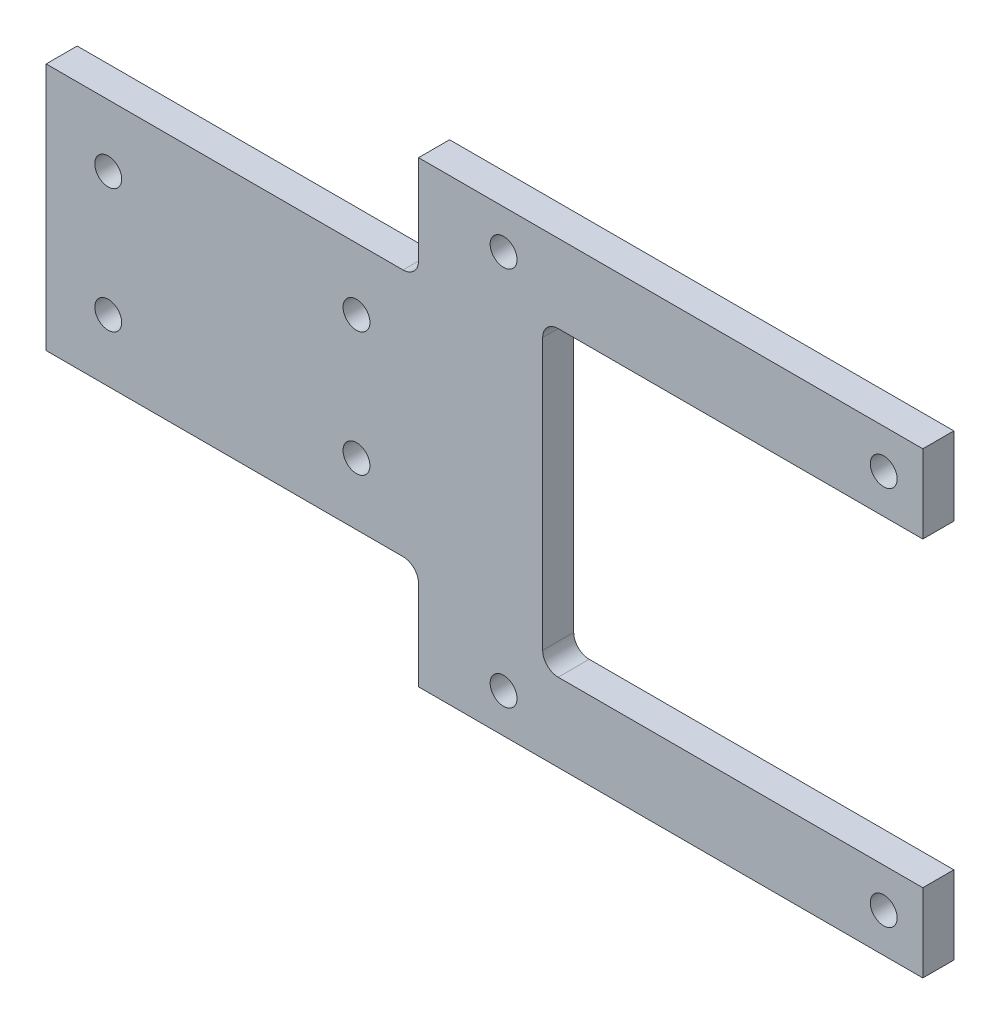
SolidWorks part; units mm, degrees
ref_plane "Front" through (0, 0, 0) normal (0, 0, 1) x (1, 0, 0)
ref_plane "Top" through (0, 0, 0) normal (0, 1, 0) x (1, 0, 0)
ref_plane "Right" through (0, 0, 0) normal (1, 0, 0) x (0, 0, -1)
sketch "Sketch1" plane through (0, 0, 0) normal (0, 0, 1) x (1, 0, 0)
  line L0 (38.1, 25.4) -> (38.1, 46.8909)
  line L1 (38.1, 25.4) -> (-38.1, 25.4)
  line L3 (38.1, -25.4) -> (-38.1, -25.4)
  line L4 (-38.1, 25.4) -> (-38.1, -25.4)
  line L5 (38.1, 25.4) -> (-38.1, -25.4) construction
  line L6 (38.1, -25.4) -> (-38.1, 25.4) construction
  line L7 (38.1, 46.8909) -> (141.2817, 46.8909)
  line L8 (141.2817, 46.8909) -> (141.2817, 30.8909)
  line L9 (141.2817, 30.8909) -> (63.5, 30.8909)
  line L10 (63.5, 30.8909) -> (63.5, -30.8909)
  line L11 (63.5, -30.8909) -> (141.2817, -30.8909)
  line L12 (141.2817, -30.8909) -> (141.2817, -46.8909)
  line L13 (141.2817, -46.8909) -> (38.1, -46.8909)
  line L14 (38.1, -46.8909) -> (38.1, -25.4)
  line L15 (38.1, 25.4) -> (63.5, 0) construction
  line L16 (63.5, 0) -> (38.1, -25.4) construction
  line L17 (0, 0) -> (94.3909, 0) construction
  line L18 (133.2817, -38.8909) -> (55.5, 38.8909) construction
  line L19 (133.2817, 38.8909) -> (55.5, -38.8909) construction
  line L20 (63.5, 30.8909) -> (94.3909, 0) construction
  line L21 (94.3909, 0) -> (63.5, -30.8909) construction
  line L22 (133.2817, 38.8909) -> (133.2817, 46.8909) construction
  line L23 (133.2817, 38.8909) -> (141.2817, 38.8909) construction
  line L24 (133.2817, 38.8909) -> (133.2817, 30.8909) construction
  line L25 (55.5, 38.8909) -> (38.1, 38.8909) construction
  circle A0 centre (94.3909, 0) radius 55 construction
  point P0 (0, 0)
  point P12 (50.1275, 29.3659)
  point P17 (133.2817, 38.8909)
  point P18 (133.2817, -38.8909)
  point P19 (55.5, 38.8909)
  point P20 (55.5, -38.8909)
  point P29 (-32.9423, 25.4)
  point P30 (44.45, 0)
  dimension "D2" = 110
  dimension "D1" = 50.8
  dimension "D3" = 45
  dimension "D4" = 45
  dimension "D5" = 90
  dimension "D6" = 8
  dimension "D7" = 76.2
  dimension "D8" = 25.4
extrude "Boss-Extrude1" add sketch "Sketch1" along normal blind 6.35
hole_wizard "M5 Clearance Hole1" positions "Sketch3" profile "Sketch4" hole size "M5" standard "ANSI Metric"
sketch "Sketch3" plane through (0, 0, 6.35) normal (0, 0, 1) x (1, 0, 0)
  line L0 (0, 0) -> (94.3909, 0) construction
  line L2 (133.2817, -38.8909) -> (55.5, 38.8909) construction
  line L4 (133.2817, 38.8909) -> (55.5, -38.8909) construction
  line L6 (63.5, 30.8909) -> (94.3909, 0) construction
  line L7 (94.3909, 0) -> (63.5, -30.8909) construction
  circle A0 centre (94.3909, 0) radius 55 construction
  point P0 (133.2817, 38.8909)
  point P2 (133.2817, -38.8909)
  point P4 (55.5, 38.8909)
  point P6 (55.5, -38.8909)
  dimension "D1" = 110
  dimension "D2" = 45
  dimension "D3" = 45
  dimension "D4" = 90
sketch "Sketch4" plane through (133.2817, 38.8909, 6.35) normal (1, 0, 0) x (0, -1, 0)
  line L0 (0, 0) -> (0, 20.4024)
  line L1 (0, 20.4024) -> (2.75, 18.75)
  line L2 (2.75, 18.75) -> (2.75, 0)
  line L5 (2.75, 0) -> (0, 0)
  line L10 (0, 20.4024) -> (-2.75, 18.75) construction
  line L11 (0, -6.35) -> (0, 107.95) construction
  dimension "Hole Dia." = 5.5
  dimension "Hole Depth" = 18.75
  dimension "Drill Angle" = 118
fillet "Fillet1" radius 3.175 4 edges at (63.5, 30.8909, 3.175) (63.5, -30.8909, 3.175) (38.1, -25.4, 3.175) (38.1, 25.4, 3.175)
hole_wizard "M5 Clearance Hole2" positions "Sketch5" profile "Sketch6" hole size "M5" standard "ANSI Metric"
sketch "Sketch5" plane through (0, 0, 6.35) normal (0, 0, 1) x (1, 0, 0)
  line L0 (-25.4, 12.7) -> (25.4, 12.7) construction
  line L1 (25.4, 12.7) -> (25.4, -12.7) construction
  line L2 (25.4, -12.7) -> (-25.4, -12.7) construction
  line L3 (-25.4, -12.7) -> (-25.4, 12.7) construction
  line L5 (34.925, 25.4) -> (-38.1, 25.4) construction
  line L6 (-38.1, -25.4) -> (34.925, -25.4) construction
  line L7 (-38.1, 25.4) -> (-38.1, -25.4) construction
  line L8 (63.5, -27.7159) -> (63.5, 27.7159) construction
  point P0 (-25.4, 12.7)
  point P2 (25.4, 12.7)
  point P4 (25.4, -12.7)
  point P6 (-25.4, -12.7)
  dimension "D1" = 12.7
  dimension "D2" = 12.7
  dimension "D3" = 12.7
  dimension "D4" = 38.1
sketch "Sketch6" plane through (-25.4, 12.7, 6.35) normal (1, 0, 0) x (0, -1, 0)
  line L0 (0, 0) -> (0, 20.4024)
  line L1 (0, 20.4024) -> (2.75, 18.75)
  line L2 (2.75, 18.75) -> (2.75, 0)
  line L5 (2.75, 0) -> (0, 0)
  line L10 (0, 20.4024) -> (-2.75, 18.75) construction
  line L11 (0, -6.35) -> (0, 107.95) construction
  dimension "Hole Dia." = 5.5
  dimension "Hole Depth" = 18.75
  dimension "Drill Angle" = 118
